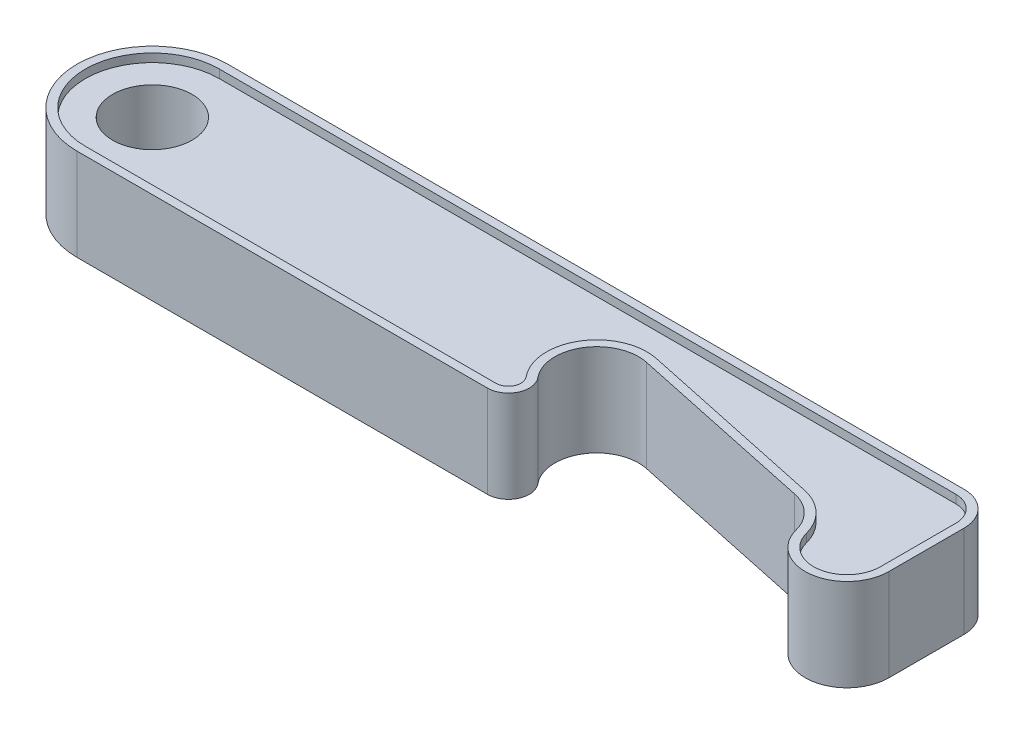
SolidWorks part; units mm, degrees
material "AISI 1020"
ref_plane "Front Plane" through (0, 0, 0) normal (0, 0, 1) x (1, 0, 0)
ref_plane "Top Plane" through (0, 0, 0) normal (0, 1, 0) x (1, 0, 0)
ref_plane "Right Plane" through (0, 0, 0) normal (1, 0, 0) x (0, 0, -1)
sketch "Sketch1" plane through (0, 0, 0) normal (0, 1, 0) x (1, 0, 0)
  line L6 (0, 9) -> (87.9997, 9)
  line L7 (91.9997, 5) -> (91.9997, -4)
  line L9 (0, -9) -> (49.0399, -9)
  line L10 (78.3568, -1.6093) -> (55.8568, 3.1733)
  line L11 (0, 8) -> (87.9997, 8)
  line L12 (90.9997, 5) -> (90.9997, -4)
  line L13 (78.5647, -0.6311) -> (56.0647, 4.1514)
  line L14 (0, -8) -> (49.0399, -8)
  arc A14 (91.9997, -4) -> (82.1585, -5.25) centre (86.9997, -4) cw
  arc A16 (55.8568, 3.1733) -> (50.9657, -4.9058) centre (54.8172, -1.7175) ccw
  arc A17 (49.0399, -9) -> (50.9657, -4.9058) centre (49.0399, -6.5) ccw
  arc A18 (0, -9) -> (0, 9) centre (0, 0) cw
  arc A19 (91.9997, 5) -> (87.9997, 9) centre (87.9997, 5) ccw
  arc A20 (82.1585, -5.25) -> (78.3568, -1.6093) centre (77.3172, -6.5) ccw
  arc A21 (90.9997, 5) -> (87.9997, 8) centre (87.9997, 5) ccw
  arc A22 (90.9997, -4) -> (83.1267, -5) centre (86.9997, -4) cw
  arc A23 (83.1267, -5) -> (78.5647, -0.6311) centre (77.3172, -6.5) ccw
  arc A24 (56.0647, 4.1514) -> (50.1954, -5.5435) centre (54.8172, -1.7175) ccw
  arc A25 (49.0399, -8) -> (50.1954, -5.5435) centre (49.0399, -6.5) ccw
  arc A26 (0, -8) -> (0, 8) centre (0, 0) cw
  circle A27 centre (0, 0) radius 4.75
  point P2 (0, 0)
  point P5 (-9, 0)
  point P18 (91.9997, 0.5)
  dimension "D1" = 100.9997
  dimension "D2" = 4
  dimension "D3" = 9
  dimension "D4" = 9.5
  dimension "D5" = 2.5
  dimension "D9" = 12
  dimension "D11" = 22.5
  dimension "D6" = 5
  dimension "D7" = 5
  dimension "D8" = 13
  dimension "D10" = 5
  dimension "D12" = 1
extrude "Boss-Extrude6" add sketch "Sketch1" along normal mid plane 11 contours A20 A14 L7 A19 L6 A18 L9 A17 A16 L10 L14 A26 L11 A21 L12 A22 A23 L13 A24 A25 region at (43.9998, 0, -8.8974)
extrude "Boss-Extrude7" add sketch "Sketch1<6>" along normal mid plane 9 contours A26 L14 A25 A24 L13 A23 A22 L12 A21 L11 region at (38.43, 0, -0.8544)
sketch "Sketch1<6>" plane through (0, 0, 0) normal (0, 1, 0) x (1, 0, 0) same geometry as "Sketch1"
